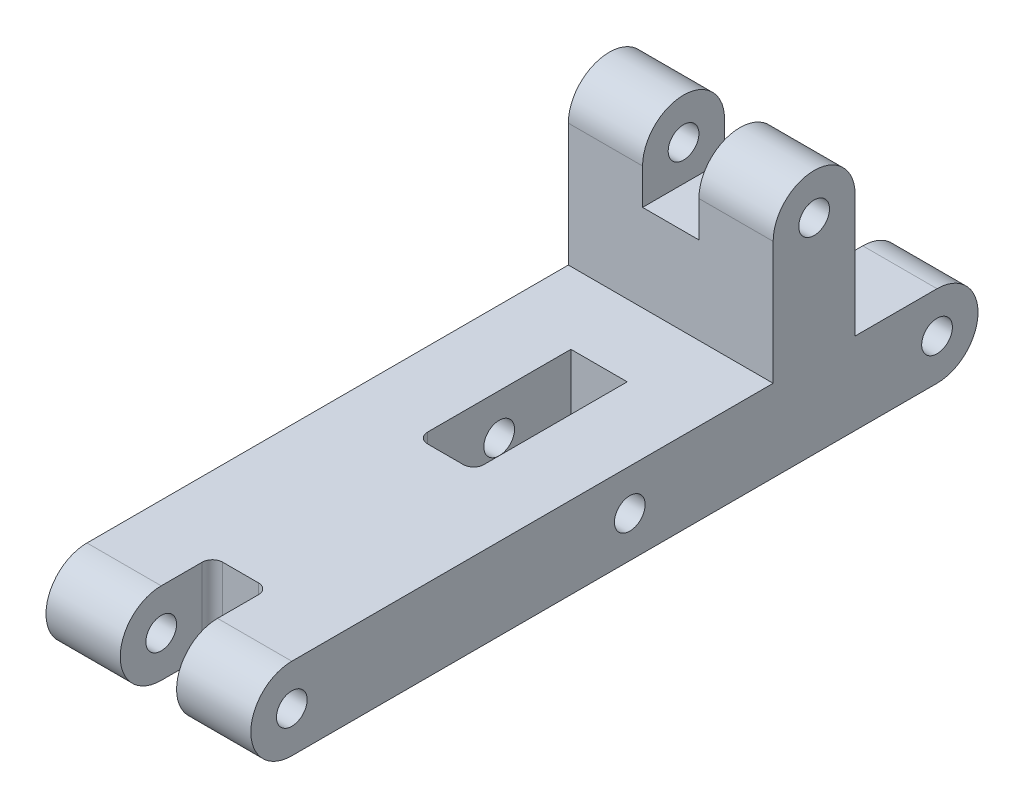
SolidWorks part; units mm, degrees
ref_plane "Alzado" through (0, 0, 0) normal (0, 0, 1) x (1, 0, 0)
ref_plane "Planta" through (0, 0, 0) normal (0, 1, 0) x (1, 0, 0)
ref_plane "Vista lateral" through (0, 0, 0) normal (1, 0, 0) x (0, 0, -1)
sketch "Croquis1" plane through (0, 0, 0) normal (1, 0, 0) x (0, 0, -1)
  line L0 (-15, 0) -> (15, 0) construction
  line L1 (-15, 4) -> (-1, 4)
  line L2 (-15, -4) -> (15, -4)
  line L3 (7, 4) -> (15, 4)
  line L5 (-1, 4) -> (-1, 16)
  line L6 (-1, 16) -> (7, 16) construction
  line L7 (7, 4) -> (7, 16)
  line L8 (-15, 4) -> (-48, 4)
  line L9 (-15, -4) -> (-48, -4)
  line L10 (-48, 4) -> (-48, -4) construction
  arc A0 (-15, 4) -> (-15, -4) centre (-15, 0) ccw construction
  arc A1 (15, -4) -> (15, 4) centre (15, 0) ccw
  circle A2 centre (15, 0) radius 1.5
  arc A3 (7, 16) -> (-1, 16) centre (3, 16) ccw
  circle A4 centre (3, 16) radius 1.5
  circle A5 centre (-15, 0) radius 1.5
  arc A6 (-48, 4) -> (-48, -4) centre (-48, 0) ccw
  circle A7 centre (-48, 0) radius 1.5
  point P3 (0, 0)
  dimension "D2" = 4
  dimension "D3" = 3
  dimension "D4" = 4
  dimension "D7" = 33
  dimension "D1" = 30
  dimension "D5" = 8
  dimension "D6" = 12
extrude "Saliente-Extruir1" add sketch "Croquis1" along normal mid plane 20
sketch "Croquis2" plane through (0, 0, 0) normal (1, 0, 0) x (0, 0, -1)
  line L0 (-1, 16) -> (-1, 4) construction
  line L1 (-1, 12.5) -> (7, 12.5)
  line L2 (-1, 12.5) -> (-1, 20)
  line L3 (-1, 20) -> (7, 20)
  line L4 (7, 12.5) -> (7, 20)
  line L5 (7, 4) -> (7, 16) construction
  line L6 (-1, 4) -> (-48, 4) construction
  line L7 (-8, 4) -> (-23, 4)
  line L8 (-8, 4) -> (-8, -4)
  line L9 (-8, -4) -> (-23, -4)
  line L10 (-23, 4) -> (-23, -4)
  line L11 (-48, -4) -> (15, -4) construction
  line L12 (15, 4) -> (7, 4) construction
  line L13 (10, 4) -> (19, 4)
  line L14 (10, 4) -> (10, -4)
  line L15 (10, -4) -> (19, -4)
  line L16 (19, 4) -> (19, -4)
  line L17 (-1, 4) -> (-48, 4) construction
  line L18 (-43, 4) -> (-52, 4)
  line L19 (-43, 4) -> (-43, -4)
  line L20 (-43, -4) -> (-52, -4)
  line L21 (-52, 4) -> (-52, -4)
  line L22 (-48, -4) -> (15, -4) construction
  arc A0 (7, 16) -> (-1, 16) centre (3, 16) ccw construction
  arc A2 (15, -4) -> (15, 4) centre (15, 0) ccw construction
  circle A4 centre (-15, 0) radius 1.5 construction
  arc A5 (-48, 4) -> (-48, -4) centre (-48, 0) ccw construction
  dimension "D5" = 9
  dimension "D1" = 7.5
  dimension "D2" = 8
  dimension "D3" = 9
  dimension "D4" = 8
extrude "Cortar-Extruir1" cut sketch "Croquis2" against normal mid plane 5.5
fillet "Redondeo1" radius 1 6 edges at (2.75, 0, 23) (-2.75, 0, 23) (2.75, 0, 43) (-2.75, 0, 43) (2.75, 0, -10) (-2.75, 0, -10)
